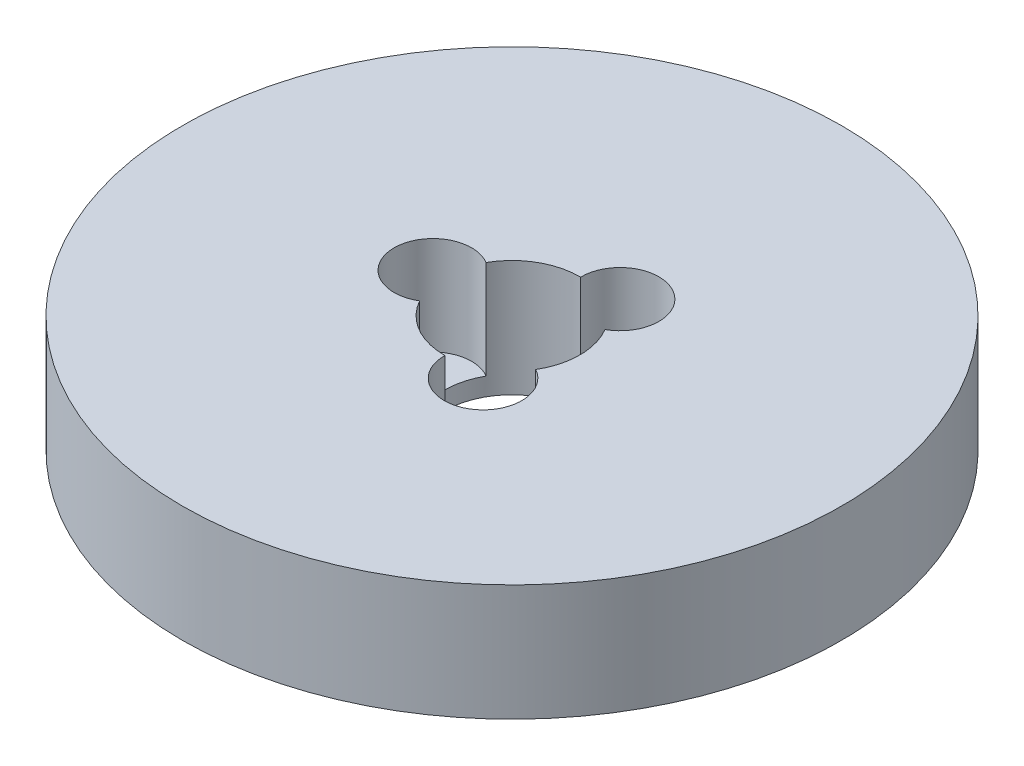
SolidWorks part; units mm, degrees
ref_plane "Front Plane" through (0, 0, 0) normal (0, 0, 1) x (1, 0, 0)
ref_plane "Top Plane" through (0, 0, 0) normal (0, 1, 0) x (1, 0, 0)
ref_plane "Right Plane" through (0, 0, 0) normal (1, 0, 0) x (0, 0, -1)
sketch "Sketch1" plane through (0, 0, 0) normal (0, 1, 0) x (1, 0, 0)
  circle A0 centre (0, 0) radius 85
  dimension "FLANGE_OD" = 170
extrude "Boss-Extrude1" add sketch "Sketch1" along normal blind 30
sketch "Sketch2" plane through (0, 0, 0) normal (0, 1, 0) x (1, 0, 0)
  circle A0 centre (0, 0) radius 17.5
  dimension "BORE_D" = 35
extrude "Cut-Extrude1" cut sketch "Sketch2" along normal through all
sketch "Sketch3" plane through (0, 30, 0) normal (0, 1, 0) x (1, 0, 0)
  circle A0 centre (0, 0) radius 20.4121 construction
  circle A1 centre (-20.4121, 0) radius 10
  dimension "BOLT_D" = 20
  dimension "BOLT_PCD" = 40.8241
extrude "Cut-Extrude2" cut sketch "Sketch3" against normal blind 25.3625
pattern_circular "CirPattern1" count 3 over 360 about axis through (0, 0, 0) along (0, 1, 0) of "Cut-Extrude2"
